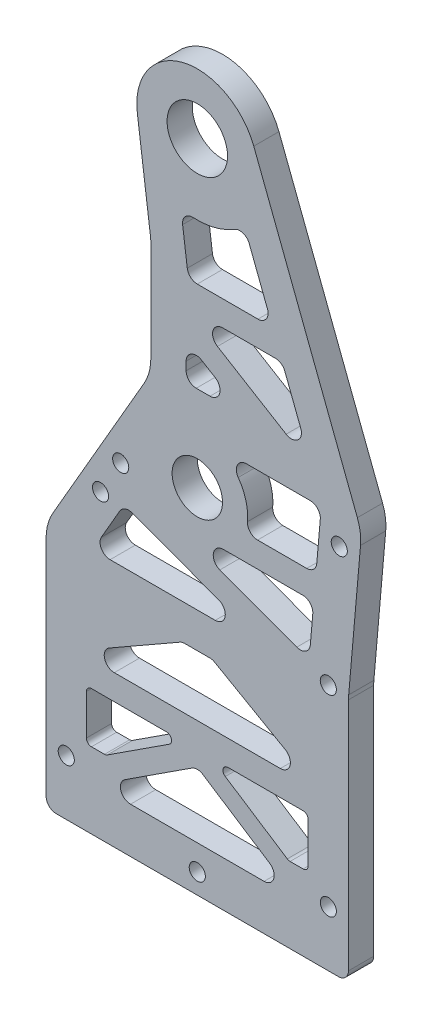
SolidWorks part; units mm, degrees
material "Thornel Mat VMA"
ref_plane "前视基准面" through (0, 0, 0) normal (0, 0, 1) x (1, 0, 0)
ref_plane "上视基准面" through (0, 0, 0) normal (0, 1, 0) x (1, 0, 0)
ref_plane "右视基准面" through (0, 0, 0) normal (1, 0, 0) x (0, 0, -1)
sketch "草图1" plane through (0, 0, 0) normal (0, 0, 1) x (1, 0, 0)
  line L0 (-30, 0) -> (30, 0)
  line L1 (30, 0) -> (30, 49)
  line L2 (30, 49) -> (32.5887, 78.5887)
  line L3 (32.5887, 78.5887) -> (11.203, 134.3004)
  line L4 (-30, 0) -> (-30, 49)
  line L5 (-30, 49) -> (-9.2154, 85)
  line L6 (-9.2154, 85) -> (-9.2154, 108)
  line L7 (0, 0) -> (0, 130) construction
  line L8 (-9.2154, 108) -> (-11.898, 128.4384)
  circle A0 centre (0, 130) radius 6
  arc A1 (11.203, 134.3004) -> (-11.898, 128.4384) centre (0, 130) ccw
  circle A2 centre (0, 4) radius 1.6
  circle A3 centre (26, 11) radius 1.6
  circle A4 centre (-26, 11) radius 1.6
  circle A5 centre (0, 70) radius 5
  circle A6 centre (-15.1962, 66.641) radius 1.6
  circle A7 centre (-19.1962, 59.7128) radius 1.6
  dimension "D8" = 130
  dimension "D9" = 12
  dimension "D10" = 24
  dimension "D13" = 3.2
  dimension "D14" = 3.2
  dimension "D15" = 3.2
  dimension "D16" = 10
  dimension "D18" = 3.2
  dimension "D19" = 3.2
  dimension "D1" = 30
  dimension "D2" = 30
  dimension "D3" = 49
  dimension "D4" = 49
  dimension "D5" = 30
  dimension "D6" = 5
  dimension "D7" = 36
  dimension "D11" = 23
  dimension "D12" = 21
  dimension "D17" = 60
extrude "凸台-拉伸1" add sketch "草图1" along normal blind 5
fillet "圆角1" radius 2 2 edges at (-30, 0, 2.5) (30, 0, 2.5)
fillet "圆角2" radius 10 5 edges at (-9.2154, 108, 2.5) (-9.2154, 85, 2.5) (-30, 49, 2.5) (32.5887, 78.5887, 2.5) (30, 49, 2.5)
sketch "草图3" plane through (0, 0, 0) normal (0, 0, -1) x (-1, 0, 0)
  line L0 (0, 0) -> (0, 206.8757) construction
  line L1 (-20, 9) -> (20, 9)
  line L2 (-20, 9) -> (0, 22)
  line L3 (28, 0) -> (-28, 0) construction
  line L4 (-30, 2) -> (-30, 48.5634) construction
  line L5 (20, 9) -> (0, 22)
  line L6 (-22, 15) -> (-18.1088, 15)
  line L7 (-18.1088, 15) -> (-2.7242, 25)
  line L8 (-2.7242, 25) -> (-22, 25)
  line L9 (-22, 25) -> (-22, 15)
  line L10 (22, 25) -> (22, 15)
  line L11 (2.7242, 25) -> (22, 25)
  line L12 (18.1088, 15) -> (2.7242, 25)
  line L13 (22, 15) -> (18.1088, 15)
  line L14 (-24, 30) -> (-3, 30)
  line L16 (-3, 42) -> (-24, 30)
  line L17 (3, 42) -> (24, 30)
  line L19 (24, 30) -> (3, 30)
  line L26 (-14.7486, 49) -> (20.7624, 49)
  line L27 (20.7624, 49) -> (14.5251, 59.8032)
  line L28 (6.036, 62) -> (-23.1068, 62)
  line L29 (-23.1068, 62) -> (-22.1953, 51.5815)
  line L30 (-30.0381, 49.4349) -> (-32.3875, 76.2888) construction
  line L31 (10.5551, 82.6795) -> (28.6603, 51.3205) construction
  line L32 (-21.9694, 49) -> (13.2568, 62) construction
  line L33 (-22.1953, 51.5815) -> (6.036, 62)
  line L34 (-14.7486, 49) -> (14.5251, 59.8032)
  line L35 (-22.1953, 51.5815) -> (-21.9694, 49) construction
  line L36 (-21.9694, 49) -> (-14.7486, 49) construction
  line L37 (6.036, 62) -> (13.2568, 62) construction
  line L38 (13.2568, 62) -> (14.5251, 59.8032) construction
  line L39 (-23.5442, 67) -> (-9.5394, 67)
  line L40 (-23.5442, 67) -> (-24.5941, 79)
  line L42 (-24.5941, 79) -> (-4.3589, 79)
  line L43 (-31.7613, 80.7441) -> (-11.203, 134.3004) construction
  line L44 (1.7616, 105) -> (-14.9523, 105)
  line L45 (-14.9523, 105) -> (-9.3542, 119.5837)
  line L46 (1.7616, 105) -> (3.2557, 116.3838)
  line L47 (11.898, 128.4384) -> (9.3004, 108.6479) construction
  line L48 (-16.8716, 100) -> (2.1284, 100)
  line L49 (2.1284, 100) -> (-22.6296, 85)
  line L50 (-22.6296, 85) -> (-16.8716, 100)
  line L51 (2.2154, 94.2066) -> (-9.6794, 87)
  line L52 (-9.6794, 87) -> (2.2154, 87)
  line L53 (2.2154, 87) -> (2.2154, 94.2066)
  line L54 (9.2154, 107.3465) -> (9.2154, 87.6795) construction
  line L55 (-3, 42) -> (3, 42)
  line L56 (-3, 30) -> (3, 30)
  arc A0 (-4.3589, 79) -> (-9.5394, 67) centre (0, 70) ccw
  arc A1 (-9.3542, 119.5837) -> (3.2557, 116.3838) centre (0, 130) ccw
  circle A2 centre (0, 70) radius 5 construction
  point P12 (0, 9)
  dimension "D21" = 10
  dimension "D26" = 28
  dimension "D1" = 9
  dimension "D2" = 10
  dimension "D3" = 13
  dimension "D4" = 6
  dimension "D5" = 8
  dimension "D6" = 4
  dimension "D7" = 10
  dimension "D8" = 5
  dimension "D9" = 12
  dimension "D10" = 3
  dimension "D11" = 6
  dimension "D12" = 7
  dimension "D16" = 8
  dimension "D17" = 8
  dimension "D18" = 13
  dimension "D19" = 2.5
  dimension "D20" = 2.5
  dimension "D22" = 5
  dimension "D23" = 8
  dimension "D25" = 12
  dimension "D27" = 7
  dimension "D28" = 7
  dimension "D29" = 25
  dimension "D30" = 7
  dimension "D31" = 5
  dimension "D32" = 19
  dimension "D33" = 6
  dimension "D34" = 8
  dimension "D35" = 7
  dimension "D36" = 5
extrude "切除-拉伸1" cut sketch "草图3" against normal through all
fillet "圆角3" radius 2 3 edges at (0, 22, 2.5) (20, 9, 2.5) (-20, 9, 2.5)
fillet "圆角4" radius 1 8 edges at (-22, 25, 2.5) (-22, 15, 2.5) (-18.1088, 15, 2.5) (-2.7242, 25, 2.5) (2.7242, 25, 2.5) (22, 25, 2.5) (22, 15, 2.5) (18.1088, 15, 2.5)
fillet "圆角5" radius 2 14 edges at (4.3589, 79, 2.5) (9.5394, 67, 2.5) (23.5442, 67, 2.5) (23.1068, 62, 2.5) (-6.036, 62, 2.5) (22.1953, 51.5815, 2.5) (14.7486, 49, 2.5) (-20.7624, 49, 2.5) (-14.5251, 59.8032, 2.5) (-3, 42, 2.5) (3, 42, 2.5) (24, 30, 2.5) (-24, 30, 2.5) (24.5941, 79, 2.5)
fillet "圆角7" radius 2 10 edges at (9.3542, 119.5837, 2.5) (-3.2557, 116.3838, 2.5) (-1.7616, 105, 2.5) (14.9523, 105, 2.5) (16.8716, 100, 2.5) (-2.1284, 100, 2.5) (-2.2154, 94.2066, 2.5) (22.6296, 85, 2.5) (9.6794, 87, 2.5) (-2.2154, 87, 2.5)
sketch "草图4" plane through (0, 0, 0) normal (0, 0, -1) x (-1, 0, 0)
  line L0 (-30.0381, 49.4349) -> (-32.3875, 76.2888) construction
  line L1 (-9.7468, 79) -> (-22.4115, 79) construction
  circle A0 centre (-25.993, 49.0951) radius 1.6
  circle A1 centre (-28.1719, 74) radius 1.6
  dimension "D1" = 3.2
  dimension "D2" = 3.2
  dimension "D3" = 4
  dimension "D4" = 4
  dimension "D5" = 25
  dimension "D6" = 5
extrude "切除-拉伸2" cut sketch "草图4" against normal through all
